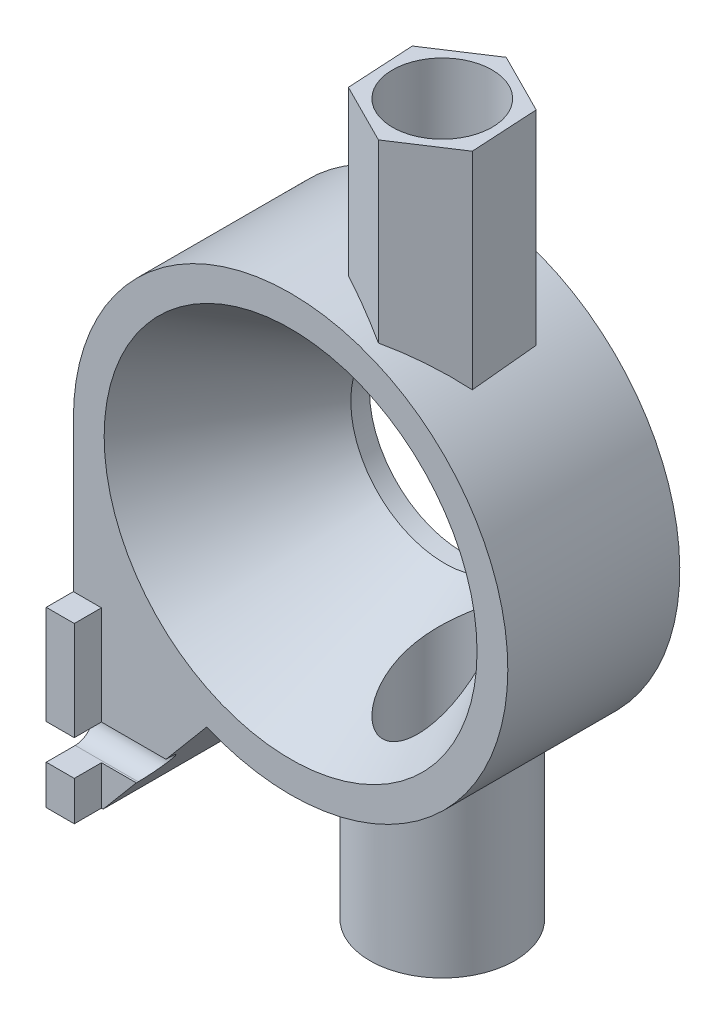
SolidWorks part; units mm, degrees
ref_plane "Front Plane" through (0, 0, 0) normal (0, 0, 1) x (1, 0, 0)
ref_plane "Top Plane" through (0, 0, 0) normal (0, 1, 0) x (1, 0, 0)
ref_plane "Right Plane" through (0, 0, 0) normal (1, 0, 0) x (0, 0, -1)
sketch "Sketch1" plane through (0, 0, 0) normal (0, 0, 1) x (1, 0, 0)
  line L0 (254.309, 185.0586) -> (255.9795, 135.0866) construction
  dimension "D1" = 50
sketch "Sketch3" plane through (0, 0, 0) normal (0, 0, 1) x (1, 0, 0)
  circle A0 centre (225, 142.5) radius 24
  dimension "D1" = 48
extrude "Boss-Extrude1" add sketch "Sketch3" along normal blind 19
sketch "Sketch5" plane through (0, 0, 0) normal (0, 0, 1) x (1, 0, 0)
  line L0 (201, 142.5) -> (201, 106.7745)
  line L1 (201, 106.7745) -> (204.2866, 106.7745)
  line L2 (204.2866, 106.7745) -> (215.7335, 120.3611)
  circle A0 centre (225, 142.5) radius 24 construction
  circle A3 centre (225, 142.5) radius 24
  arc A4 (201, 142.5) -> (215.7335, 120.3611) centre (225, 142.5) ccw
  dimension "D1" = 0
extrude "Boss-Extrude2" add sketch "Sketch5" along normal blind 19
ref_plane "Plane1" through (0, 0, 10) normal (0, 0, 1) x (1, 0, 0)
ref_plane "Plane2" through (0, 118.5, 0) normal (0, -1, 0) x (-1, 0, 0)
ref_plane "Plane3" through (0, 128.5, 0) normal (0, -1, 0) x (-1, 0, 0)
sketch "Sketch7" plane through (0, 128.5, 0) normal (0, -1, 0) x (-1, 0, 0)
  line L1 (-240.76, 10.454) -> (-240.76, -27.7584) construction
  line L4 (-26.8798, -10) -> (26.8798, -10) construction
  line L5 (-201, -19) -> (-201, 0) construction
  circle A1 centre (-232.76, -10) radius 8
  dimension "D1" = 16
  dimension "D2" = 39.76
extrude "Boss-Extrude3" add sketch "Sketch7" along normal blind 22.5
ref_plane "Plane4" through (0, 158.5, 0) normal (0, -1, 0) x (-1, 0, 0)
sketch "Sketch8" plane through (0, 158.5, 0) normal (0, -1, 0) x (-1, 0, 0)
  line L1 (-239.0279, -5.8947) -> (-239.4492, -13.3755)
  line L2 (-239.4492, -13.3755) -> (-233.1813, -17.4808)
  line L3 (-233.1813, -17.4808) -> (-226.4921, -14.1053)
  line L4 (-226.4921, -14.1053) -> (-226.0708, -6.6245)
  line L5 (-226.0708, -6.6245) -> (-232.3387, -2.5192)
  line L6 (-232.3387, -2.5192) -> (-239.0279, -5.8947)
  circle A0 centre (-232.76, -10) radius 6.4888 construction
  circle A1 centre (-232.76, -10) radius 8 construction
extrude "Boss-Extrude4" add sketch "Sketch8" against normal blind 26
sketch "Sketch9" plane through (201, 0, 0) normal (-1, 0, 0) x (0, 0, 1)
  line L0 (0, 142.5) -> (0, 106.7745) construction
  line L1 (19, 106.7745) -> (22, 106.7745)
  line L2 (19, 106.7745) -> (19, 125.9445)
  line L3 (19, 125.9445) -> (22, 125.9445)
  line L4 (22, 106.7745) -> (22, 125.9445)
  dimension "D1" = 22
  dimension "D2" = 19.17
extrude "Boss-Extrude5" add sketch "Sketch9" against normal blind 3.1
sketch "Sketch10" plane through (201, 0, 0) normal (-1, 0, 0) x (0, 0, 1)
  line L0 (5.15, 113.0695) -> (5.15, 122.2677) construction
  line L1 (16.85, 113.0695) -> (16.85, 122.2677) construction
  line L2 (11, 127.8393) -> (11, 106.4652) construction
  line L3 (0, 142.5) -> (0, 106.7745) construction
  line L4 (22, 106.7745) -> (22, 125.9445) construction
  line L5 (3.205, 111.1245) -> (18.795, 111.1245) construction
  line L6 (22, 106.7745) -> (0, 106.7745) construction
  line L9 (0, 142.5) -> (0, 106.7745)
  line L10 (0, 115.0145) -> (0, 111.1245)
  line L11 (3.205, 115.0145) -> (0, 115.0145)
  line L12 (22, 106.7745) -> (22, 125.9445)
  line L13 (22, 111.1245) -> (22, 115.0145)
  line L14 (3.205, 111.1245) -> (0, 111.1245)
  line L15 (18.795, 115.0145) -> (22, 115.0145)
  line L16 (18.795, 111.1245) -> (22, 111.1245)
  arc A0 (3.205, 111.1245) -> (3.205, 115.0145) centre (3.205, 113.0695) ccw
  arc A1 (18.795, 115.0145) -> (18.795, 111.1245) centre (18.795, 113.0695) ccw
  dimension "D3" = 3.89
  dimension "D1" = 11.7
  dimension "D2" = 4.35
  dimension "D4" = 0
  dimension "D5" = 0
extrude "Cut-Extrude1" cut sketch "Sketch10" against normal blind 15
sketch "Sketch15" plane through (0, 0, 0) normal (0, 0, -1) x (-1, 0, 0)
  circle A0 centre (-225, 142.5) radius 21.7
  arc A1 (-201, 142.5) -> (-215.7335, 120.3611) centre (-225, 142.5) ccw construction
  dimension "D1" = 2.3
extrude "Cut-Extrude3" cut sketch "Sketch15" against normal blind 2
sketch "Sketch17" plane through (0, 0, 2) normal (0, 0, -1) x (-1, 0, 0)
  circle A0 centre (-225, 142.5) radius 12.95
  circle A1 centre (-225, 142.5) radius 10.35
  circle A2 centre (-225, 142.5) radius 21.7 construction
  dimension "D1" = 20.7
  dimension "D2" = 25.9
extrude "Boss-Extrude9" add sketch "Sketch17" along normal blind 2.06
ref_axis "Axis3" through (225, 142.5, 19) along (0, 0, -1)
ref_plane "Plane5" through (225, 0, 0) normal (1, 0, 0) x (0, 0, -1)
sketch "Sketch21" plane through (225, 0, 0) normal (1, 0, 0) x (0, 0, -1)
  line L0 (-19, 163.1) -> (-19, 142.5)
  line L1 (-19, 166.5) -> (-19, 118.5) construction
  line L2 (-19, 142.5) -> (-2, 142.5)
  line L3 (-19, 142.5) -> (0, 142.5) construction
  line L6 (-2, 132.15) -> (-2, 152.85) construction
  line L8 (-19, 163.1) -> (-2, 152.85)
  line L10 (-2, 142.5) -> (-2, 152.85)
  dimension "D1" = 3.4
  dimension "D2" = 0
revolve "Cut-Revolve2" cut sketch "Sketch21" angle 360 about axis through (225, 142.5, 19) along (0, 0, -1)
sketch "Sketch24" plane through (0, 106, 0) normal (0, -1, 0) x (1, 0, 0)
  circle A0 centre (232.76, 10) radius 5.5
  circle A1 centre (232.76, 10) radius 8 construction
  dimension "D1" = 11
extrude "Cut-Extrude5" cut sketch "Sketch24" against normal through all
sketch "Sketch25" plane through (0, 0, 0) normal (0, 0, -1) x (-1, 0, 0)
  line L0 (89.7447, 588.4123) -> (11.2588, 169.0266) construction
sketch "Sketch27" plane through (0, 0, 0) normal (0, 0, -1) x (-1, 0, 0)
  line L0 (-220.764, 163.7825) -> (-220.3151, 166.0383)
  line L1 (-224.7682, 164.1988) -> (-224.7436, 166.4986)
  line L2 (-221.2632, 121.1242) -> (-220.8671, 118.8585)
  line L3 (-225.2742, 120.8017) -> (-225.3033, 118.5019)
  arc A2 (-201, 142.5) -> (-215.7335, 120.3611) centre (-225, 142.5) ccw
  arc A3 (-220.3151, 166.0383) -> (-224.7436, 166.4986) centre (-225, 142.5) ccw
  arc A4 (-225.3033, 118.5019) -> (-220.8671, 118.8585) centre (-225, 142.5) ccw
  circle A5 centre (-225, 142.5) radius 21.7
  arc A6 (-225.2742, 120.8017) -> (-221.2632, 121.1242) centre (-225, 142.5) ccw
  arc A7 (-220.764, 163.7825) -> (-224.7682, 164.1988) centre (-225, 142.5) ccw
  dimension "D3" = 10.645
  dimension "D4" = 10.64
  dimension "D1" = 0
  dimension "D2" = 0
extrude "Boss-Extrude11" add sketch "Sketch27" along normal blind 1.5
